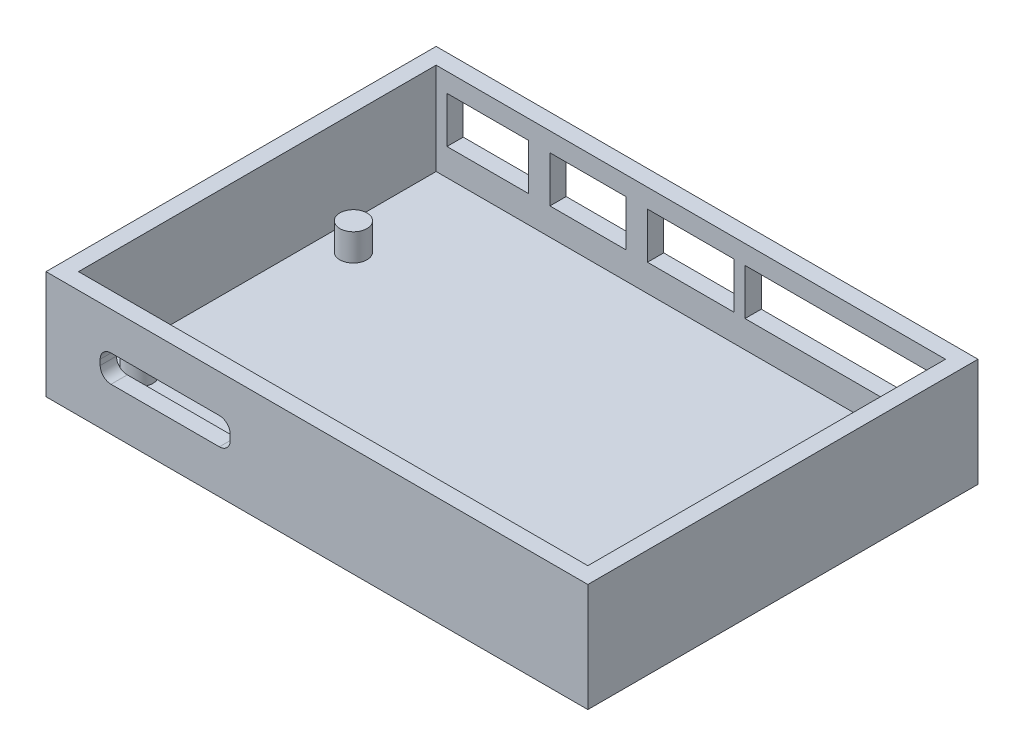
SolidWorks part; units mm, degrees
ref_plane "Front" through (0, 0, 0) normal (0, 0, 1) x (1, 0, 0)
ref_plane "Top" through (0, 0, 0) normal (0, 1, 0) x (1, 0, 0)
ref_plane "Right" through (0, 0, 0) normal (1, 0, 0) x (0, 0, -1)
sketch "Sketch1" plane through (0, 0, 0) normal (0, 1, 0) x (1, 0, 0)
  line L1 (-49.1968, 43.2851) -> (50.8032, 43.2851)
  line L2 (-49.1968, 43.2851) -> (-49.1968, -28.7149)
  line L3 (-49.1968, -28.7149) -> (50.8032, -28.7149)
  line L4 (50.8032, 43.2851) -> (50.8032, -28.7149)
  dimension "D1" = 100
  dimension "D2" = 72
extrude "Boss-Extrude1" add sketch "Sketch1" along normal blind 20
sketch "Sketch2" plane through (0, 20, 0) normal (0, 1, 0) x (1, 0, 0)
  line L0 (50.8032, 43.2851) -> (-49.1968, 43.2851) construction
  line L1 (-46.1968, 40.2851) -> (47.8032, 40.2851)
  line L2 (-46.1968, 40.2851) -> (-46.1968, -25.7149)
  line L3 (-46.1968, -25.7149) -> (47.8032, -25.7149)
  line L4 (47.8032, 40.2851) -> (47.8032, -25.7149)
  line L5 (-49.1968, 43.2851) -> (-49.1968, -28.7149) construction
  line L6 (-49.1968, -28.7149) -> (50.8032, -28.7149) construction
  line L7 (50.8032, -28.7149) -> (50.8032, 43.2851) construction
  dimension "D1" = 3
  dimension "D2" = 3
  dimension "D3" = 3
  dimension "D4" = 3
extrude "Cut-Extrude1" cut sketch "Sketch2" against normal blind 17
sketch "Sketch3" plane through (0, 3, 0) normal (0, 1, 0) x (1, 0, 0)
  line L0 (-46.1968, -25.7149) -> (47.8032, -25.7149) construction
  line L1 (-46.1968, -25.7149) -> (47.8032, -25.7149) construction
  line L2 (47.8032, 40.2851) -> (-46.1968, 40.2851) construction
  circle A0 centre (-40.9628, -19.7149) radius 2.5
  circle A1 centre (-40.9628, 19.7851) radius 2.5
  circle A2 centre (43.0372, -17.7149) radius 2.5
  circle A3 centre (43.0372, 19.7851) radius 2.5
  dimension "D1" = 5
  dimension "D3" = 5
  dimension "D4" = 5
  dimension "D9" = 5
  dimension "D2" = 6
  dimension "D5" = 8
  dimension "D6" = 84
  dimension "D7" = 39.5
  dimension "D8" = 20.5
  dimension "D10" = 84
  dimension "D11" = 37.5
extrude "Boss-Extrude2" add sketch "Sketch3" along normal blind 5
sketch "Sketch6" plane through (0, 0, -43.2851) normal (0, 0, -1) x (-1, 0, 0)
  line L1 (-46.8032, 16.5) -> (-10.8032, 16.5)
  line L2 (-46.8032, 16.5) -> (-46.8032, 8)
  line L3 (-46.8032, 8) -> (-10.8032, 8)
  line L4 (-10.8032, 16.5) -> (-10.8032, 8)
  line L19 (11.1968, 16.5) -> (25.1968, 16.5)
  line L20 (11.1968, 16.5) -> (11.1968, 8)
  line L21 (11.1968, 8) -> (25.1968, 8)
  line L22 (25.1968, 16.5) -> (25.1968, 8)
  line L23 (-8.8032, 16.5) -> (7.1968, 16.5)
  line L24 (-8.8032, 16.5) -> (-8.8032, 8)
  line L25 (-8.8032, 8) -> (7.1968, 8)
  line L26 (7.1968, 16.5) -> (7.1968, 8)
  line L27 (29.1968, 16.5) -> (44.1968, 16.5)
  line L28 (29.1968, 16.5) -> (29.1968, 8)
  line L29 (29.1968, 8) -> (44.1968, 8)
  line L30 (44.1968, 16.5) -> (44.1968, 8)
  line L31 (-50.8032, 20) -> (-50.8032, 0) construction
  line L32 (-50.8032, 20) -> (49.1968, 20) construction
  line L33 (-50.8032, 0) -> (49.1968, 0) construction
  dimension "D1" = 4
  dimension "D2" = 40
  dimension "D3" = 42
  dimension "D4" = 58
  dimension "D5" = 62
  dimension "D6" = 76
  dimension "D7" = 80
  dimension "D8" = 95
  dimension "D9" = 3.5
  dimension "D10" = 8
extrude "Boss-Extrude4" add sketch "Sketch6" against normal blind 12 contours L26 L23 L24 L25 | L22 L19 L20 L21 | L30 L27 L28 L29 | L2 L1 L4 L3 region at (-18.1968, 12.25, -43.2851) region at (0.8032, 12.25, -43.2851) region at (-36.6968, 12.25, -43.2851)
extrude "Cut-Extrude2" cut sketch "Sketch6<6>" against normal blind 18
sketch "Sketch6<6>" plane through (0, 0, -43.2851) normal (0, 0, -1) x (-1, 0, 0) same geometry as "Sketch6"
sketch "usb type-c" plane through (0, 0, 28.7149) normal (0, 0, 1) x (1, 0, 0)
  line L0 (-49.1968, 20) -> (-49.1968, 0) construction
  line L1 (-37.1968, 13) -> (-17.1968, 13)
  line L2 (-39.1968, 11) -> (-39.1968, 10)
  line L3 (-37.1968, 8) -> (-17.1968, 8)
  line L4 (-15.1968, 11) -> (-15.1968, 10)
  line L5 (-49.1968, 20) -> (50.8032, 20) construction
  arc A0 (-17.1968, 8) -> (-15.1968, 10) centre (-17.1968, 10) ccw
  arc A1 (-17.1968, 13) -> (-15.1968, 11) centre (-17.1968, 11) cw
  arc A2 (-39.1968, 10) -> (-37.1968, 8) centre (-37.1968, 10) ccw
  arc A3 (-37.1968, 13) -> (-39.1968, 11) centre (-37.1968, 11) ccw
  point P4 (-39.1968, 10.5)
  point P7 (-15.1968, 10.5)
  point P8 (-27.1968, 8)
  point P11 (-27.1968, 13)
  point P12 (0, 0)
  dimension "D5" = 2
  dimension "D1" = 10
  dimension "D2" = 34
  dimension "D3" = 12
  dimension "D4" = 7
extrude "Cut-Extrude4" cut sketch "usb type-c" against normal blind 18
